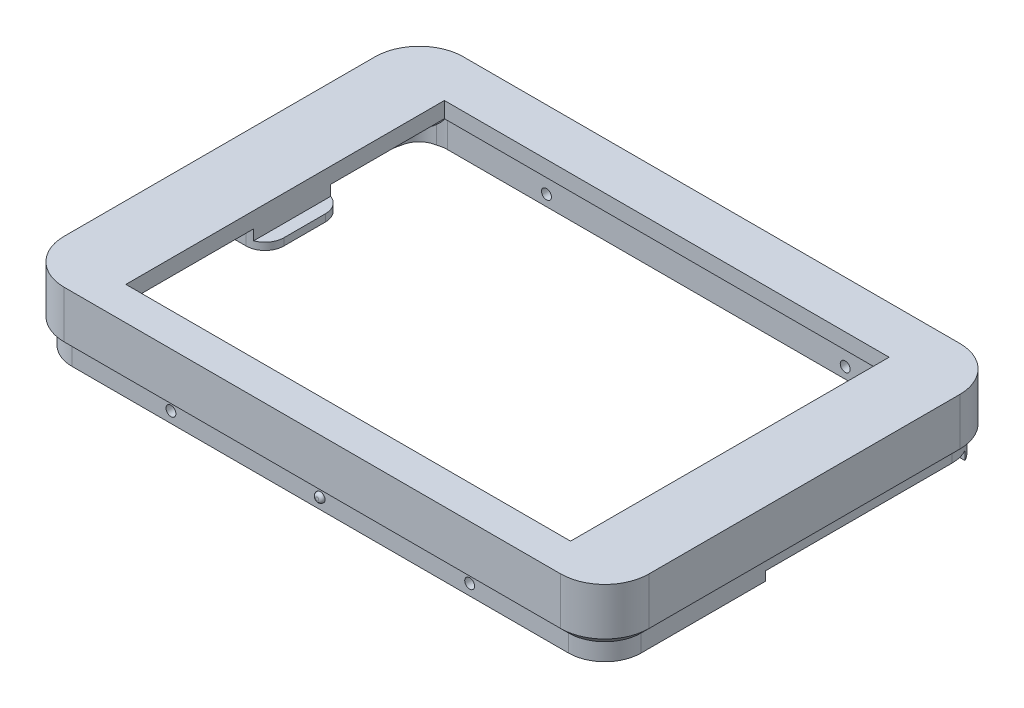
SolidWorks part; units mm, degrees
ref_plane "Front Plane" through (0, 0, 0) normal (0, 0, 1) x (1, 0, 0)
ref_plane "Top Plane" through (0, 0, 0) normal (0, 1, 0) x (1, 0, 0)
ref_plane "Right Plane" through (0, 0, 0) normal (1, 0, 0) x (0, 0, -1)
sketch "Sketch1" plane through (0, 0, 0) normal (0, 1, 0) x (1, 0, 0)
  line L0 (46.3567, -24.641) -> (46.3567, 24.641)
  line L1 (39.3567, 31.641) -> (-39.3567, 31.641)
  line L2 (-46.3567, 24.641) -> (-46.3567, -24.641)
  line L3 (-39.3567, -31.641) -> (39.3567, -31.641)
  arc A0 (46.3567, 24.641) -> (39.3567, 31.641) centre (39.3567, 24.641) ccw
  arc A1 (-39.3567, 31.641) -> (-46.3567, 24.641) centre (-39.3567, 24.641) ccw
  arc A2 (-46.3567, -24.641) -> (-39.3567, -31.641) centre (-39.3567, -24.641) ccw
  arc A3 (39.3567, -31.641) -> (46.3567, -24.641) centre (39.3567, -24.641) ccw
extrude "Boss-Extrude1" add sketch "Sketch1" along normal blind 4.5
shell "Shell1" thickness 2.5 removed face at (0, 0, 0)
sketch "Sketch2" plane through (0, 4.5, 0) normal (0, 1, 0) x (1, 0, 0)
  line L0 (39.3567, 31.641) -> (-39.3567, 31.641) construction
  line L1 (-34.8567, 24.141) -> (35.6433, 24.141)
  line L2 (-34.8567, 24.141) -> (-34.8567, -26.359)
  line L3 (-34.8567, -26.359) -> (35.6433, -26.359)
  line L4 (35.6433, 24.141) -> (35.6433, -26.359)
  line L6 (-43.8567, 24.641) -> (-43.8567, -24.641) construction
  dimension "D1" = 70.5
  dimension "D2" = 50.5
  dimension "D3" = 7.5
  dimension "D4" = 9
extrude "Cut-Extrude1" cut sketch "Sketch2" against normal blind 6
fillet "Fillet1" radius 2 8 edges at (42.5387, 2, 27.823) (0, 2, 29.141) (-42.5387, 2, 27.823) (-43.8567, 2, 0) (-42.5387, 2, -27.823) (0, 2, -29.141) (42.5387, 2, -27.823) (43.8567, 2, 0)
sketch "Sketch3" plane through (0, 2, 0) normal (0, -1, 0) x (1, 0, 0)
  circle A0 centre (-40.3931, 23.336) radius 1.25
  circle A1 centre (-40.3931, 23.336) radius 3.25
  circle A2 centre (-40.3931, -25.664) radius 1.25
  circle A3 centre (-40.3931, -25.664) radius 3.25
  circle A4 centre (37.6385, -25.664) radius 1.25
  circle A5 centre (37.6385, -25.664) radius 3.25
  circle A6 centre (37.6385, 23.336) radius 1.25
  circle A7 centre (37.6385, 23.336) radius 3.25
  dimension "D1" = 2
  dimension "D2" = 2
  dimension "D3" = 2
  dimension "D4" = 2
extrude "Boss-Extrude2" add sketch "Sketch3" along normal blind 2.5
sketch "Sketch4" plane through (0, 0, 0) normal (0, -1, 0) x (1, 0, 0)
  line L0 (39.3567, 29.141) -> (-39.3567, 29.141)
  line L1 (-43.8567, 24.641) -> (-43.8567, -24.641)
  line L2 (-39.3567, -29.141) -> (39.3567, -29.141)
  line L3 (43.8567, -24.641) -> (43.8567, 24.641)
  line L4 (39.3567, 31.641) -> (-39.3567, 31.641)
  line L5 (-46.3567, 24.641) -> (-46.3567, -24.641)
  line L6 (-39.3567, -31.641) -> (39.3567, -31.641)
  line L7 (46.3567, -24.641) -> (46.3567, 24.641)
  line L8 (39.3567, 31.641) -> (-39.3567, 31.641)
  line L9 (-46.3567, 24.641) -> (-46.3567, -24.641)
  line L10 (-39.3567, -31.641) -> (39.3567, -31.641)
  line L11 (46.3567, -24.641) -> (46.3567, 24.641)
  arc A0 (-39.3567, 29.141) -> (-43.8567, 24.641) centre (-39.3567, 24.641) ccw
  arc A1 (-43.8567, -24.641) -> (-39.3567, -29.141) centre (-39.3567, -24.641) ccw
  arc A2 (39.3567, -29.141) -> (43.8567, -24.641) centre (39.3567, -24.641) ccw
  arc A3 (43.8567, 24.641) -> (39.3567, 29.141) centre (39.3567, 24.641) ccw
  arc A4 (46.3567, 24.641) -> (39.3567, 31.641) centre (39.3567, 24.641) ccw
  arc A5 (-39.3567, 31.641) -> (-46.3567, 24.641) centre (-39.3567, 24.641) ccw
  arc A6 (-46.3567, -24.641) -> (-39.3567, -31.641) centre (-39.3567, -24.641) ccw
  arc A7 (39.3567, -31.641) -> (46.3567, -24.641) centre (39.3567, -24.641) ccw
  arc A8 (46.3567, 24.641) -> (39.3567, 31.641) centre (39.3567, 24.641) ccw
  arc A9 (-39.3567, 31.641) -> (-46.3567, 24.641) centre (-39.3567, 24.641) ccw
  arc A10 (-46.3567, -24.641) -> (-39.3567, -31.641) centre (-39.3567, -24.641) ccw
  arc A11 (39.3567, -31.641) -> (46.3567, -24.641) centre (39.3567, -24.641) ccw
  dimension "D1" = 0
  dimension "D2" = 2.5
extrude "Boss-Extrude3" add sketch "Sketch4" along normal blind 3
sketch "Sketch5" plane through (-34.8567, 0, 0) normal (1, 0, 0) x (0, 0, -1)
  line L1 (-6.2748, 0.3532) -> (6.2927, 0.3532)
  line L2 (-6.2748, 0.3532) -> (-6.2748, 2)
  line L3 (-6.2748, 2) -> (6.2927, 2)
  line L4 (6.2927, 0.3532) -> (6.2927, 2)
extrude "Boss-Extrude4" add sketch "Sketch5" against normal blind 4
sketch "Sketch6" plane through (0, 0, 6.2748) normal (0, 0, 1) x (1, 0, 0)
  line L0 (-34.8567, 0.3532) -> (-32.8849, 0.3532)
  line L1 (-32.8849, 0.3532) -> (-32.8849, -0.7856)
  line L2 (-32.8849, -0.7856) -> (-38.3084, -0.7856)
  line L3 (-38.3084, -0.7856) -> (-38.8567, 0.3532)
  line L4 (-38.8567, 0.3532) -> (-34.8567, 0.3532)
extrude "Boss-Extrude5" add sketch "Sketch6" against normal up to surface (12.5674 mm away) up to face at (-36.8567, 1.1766, -6.2927)
fillet "Fillet4" radius 3 2 edges at (-32.8849, -0.2162, -6.2927) (-32.8849, -0.2162, 6.2748)
sketch "Sketch8" plane through (0, 4.5, 0) normal (0, 1, 0) x (1, 0, 0)
  line L1 (-34.8567, 24.141) -> (35.6433, 24.141)
  line L2 (-34.8567, 24.141) -> (-34.8567, -26.359)
  line L3 (-34.8567, -26.359) -> (35.6433, -26.359)
  line L4 (35.6433, 24.141) -> (35.6433, -26.359)
extrude "Cut-Extrude2" cut sketch "Sketch8" against normal blind 4
sketch "Sketch10" plane through (0, -3, 0) normal (0, -1, 0) x (1, 0, 0)
  line L4 (-39.3567, -29.141) -> (39.3567, -29.141) construction
  line L5 (43.8567, -24.641) -> (43.8567, 24.641) construction
  line L6 (39.3567, 29.141) -> (-39.3567, 29.141) construction
  line L7 (-43.8567, 24.641) -> (-43.8567, -24.641) construction
  line L8 (-39.3567, -29.141) -> (39.3567, -29.141)
  line L9 (43.8567, -24.641) -> (43.8567, 24.641)
  line L10 (39.3567, 29.141) -> (-39.3567, 29.141)
  line L11 (-43.8567, 24.641) -> (-43.8567, -24.641)
  line L12 (-39.3567, -30.391) -> (39.3567, -30.391)
  line L13 (45.1067, -24.641) -> (45.1067, 24.641)
  line L14 (39.3567, 30.391) -> (-39.3567, 30.391)
  line L15 (-45.1067, 24.641) -> (-45.1067, -24.641)
  arc A4 (39.3567, -29.141) -> (43.8567, -24.641) centre (39.3567, -24.641) ccw construction
  arc A5 (43.8567, 24.641) -> (39.3567, 29.141) centre (39.3567, 24.641) ccw construction
  arc A6 (-39.3567, 29.141) -> (-43.8567, 24.641) centre (-39.3567, 24.641) ccw construction
  arc A7 (-43.8567, -24.641) -> (-39.3567, -29.141) centre (-39.3567, -24.641) ccw construction
  arc A8 (39.3567, -29.141) -> (43.8567, -24.641) centre (39.3567, -24.641) ccw
  arc A9 (43.8567, 24.641) -> (39.3567, 29.141) centre (39.3567, 24.641) ccw
  arc A10 (-39.3567, 29.141) -> (-43.8567, 24.641) centre (-39.3567, 24.641) ccw
  arc A11 (-43.8567, -24.641) -> (-39.3567, -29.141) centre (-39.3567, -24.641) ccw
  arc A12 (39.3567, -30.391) -> (45.1067, -24.641) centre (39.3567, -24.641) ccw
  arc A13 (45.1067, 24.641) -> (39.3567, 30.391) centre (39.3567, 24.641) ccw
  arc A14 (-39.3567, 30.391) -> (-45.1067, 24.641) centre (-39.3567, 24.641) ccw
  arc A15 (-45.1067, -24.641) -> (-39.3567, -30.391) centre (-39.3567, -24.641) ccw
  dimension "D1" = 1.25
extrude "Boss-Extrude6" add sketch "Sketch10" along normal blind 4
chamfer "Chamfer1" distance 1.25 angle 45 8 edges at (0, -3, 30.391) (-43.4226, -3, 28.7069) (43.4226, -3, 28.7069) (-45.1067, -3, 0) (45.1067, -3, 0) (-43.4226, -3, -28.7069) (43.4226, -3, -28.7069) (0, -3, -30.391)
sketch "Sketch11" plane through (0, 4.5, 0) normal (0, 1, 0) x (1, 0, 0)
  line L0 (35.6433, 24.141) -> (-34.8567, 24.141) construction
  line L1 (20.156, 24.141) -> (35.6433, 24.141)
  line L2 (20.156, 24.141) -> (20.156, -26.359)
  line L3 (20.156, -26.359) -> (35.6433, -26.359)
  line L4 (35.6433, 24.141) -> (35.6433, -26.359)
extrude "Cut-Extrude3" cut sketch "Sketch11" against normal blind 24
sketch "Sketch12" plane through (0, -7, 0) normal (0, -1, 0) x (1, 0, 0)
  line L1 (-39.9799, -25.3582) -> (-48.5649, -25.3582)
  line L2 (-39.9799, -25.3582) -> (-39.9799, -33.6082)
  line L3 (-39.9799, -33.6082) -> (-48.5649, -33.6082)
  line L4 (-48.5649, -25.3582) -> (-48.5649, -33.6082)
sketch "Sketch13" plane through (0, -7, 0) normal (0, -1, 0) x (1, 0, 0)
  circle A0 centre (-40.3931, -25.664) radius 3.25
extrude "Cut-Extrude4" cut sketch "Sketch13" against normal up to surface (6.5 mm away) up to face at (-40.3931, -0.5, -26.914)
sketch "Sketch14" plane through (0, 0, -30.391) normal (0, 0, -1) x (-1, 0, 0)
  circle A0 centre (0, -5.25) radius 0.75
extrude "Boss-Extrude7" add sketch "Sketch14" along normal blind 0.5
fillet "Fillet5" radius 0.5 1 edges at (-0.75, -5.25, -30.891)
sketch "Sketch15" plane through (0, 0, 30.391) normal (0, 0, 1) x (1, 0, 0)
  circle A0 centre (0, -5.25) radius 0.75
extrude "Boss-Extrude8" add sketch "Sketch15" along normal blind 0.5
fillet "Fillet6" radius 0.5 1 edges at (0.75, -5.25, 30.891)
sketch "Sketch16" plane through (45.1067, 0, 0) normal (1, 0, 0) x (0, 0, -1)
  line L1 (-4.8925, -5.5711) -> (27.4665, -5.5711)
  line L2 (-4.8925, -5.5711) -> (-4.8925, -7.3216)
  line L3 (-4.8925, -7.3216) -> (27.4665, -7.3216)
  line L4 (27.4665, -5.5711) -> (27.4665, -7.3216)
extrude "Cut-Extrude5" cut sketch "Sketch16" against normal blind 20.5
sketch "Sketch17" plane through (0, 0, -30.391) normal (0, 0, -1) x (-1, 0, 0)
  circle A0 centre (23.6797, -5.2689) radius 0.7839
  circle A1 centre (-23.6797, -5.2689) radius 0.7839
extrude "Cut-Extrude6" cut sketch "Sketch17" against normal through all
